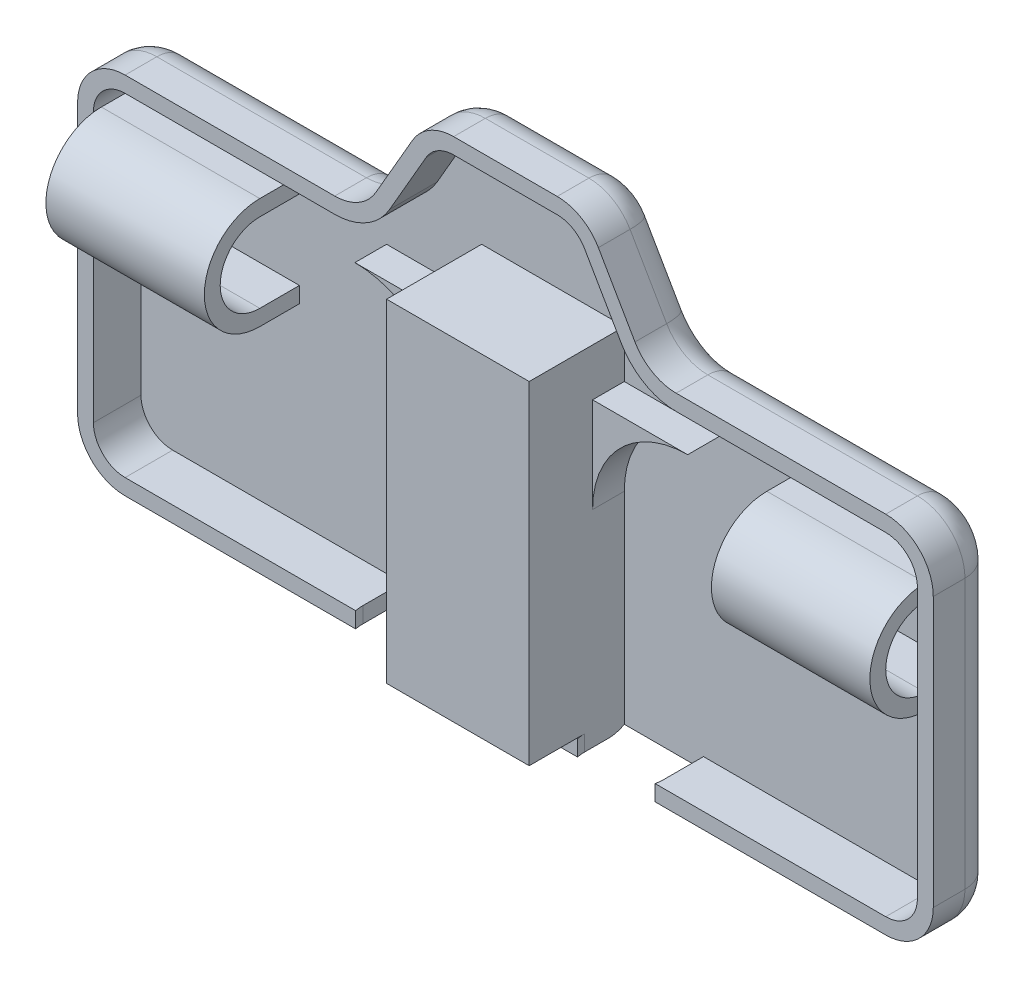
SolidWorks part; units mm, degrees
material "PA Type 6"
ref_plane "Front Plane" through (0, 0, 0) normal (0, 0, 1) x (1, 0, 0)
ref_plane "Top Plane" through (0, 0, 0) normal (0, 1, 0) x (1, 0, 0)
ref_plane "Right Plane" through (0, 0, 0) normal (1, 0, 0) x (0, 0, -1)
sketch "Sketch2" plane through (0, 0, 0) normal (0, 0, 1) x (1, 0, 0)
  line L0 (-3.2679, 18.5) -> (3.2679, 18.5)
  line L1 (-24, 11.5) -> (-10.7735, 11.5)
  line L2 (-27, 8.5) -> (-27, -8.5)
  line L3 (-24, -11.5) -> (24, -11.5)
  line L4 (27, 8.5) -> (27, -8.5)
  line L5 (-27, 11.5) -> (27, -11.5) construction
  line L6 (-27, -11.5) -> (27, 11.5) construction
  line L7 (-5.866, 17) -> (-8.1754, 13)
  line L8 (5.866, 17) -> (8.1754, 13)
  line L9 (10.7735, 11.5) -> (24, 11.5)
  arc A0 (24, -11.5) -> (27, -8.5) centre (24, -8.5) ccw
  arc A1 (-27, -8.5) -> (-24, -11.5) centre (-24, -8.5) ccw
  arc A2 (24, 11.5) -> (27, 8.5) centre (24, 8.5) cw
  arc A3 (8.1754, 13) -> (10.7735, 11.5) centre (10.7735, 14.5) ccw
  arc A4 (3.2679, 18.5) -> (5.866, 17) centre (3.2679, 15.5) cw
  arc A5 (-3.2679, 18.5) -> (-5.866, 17) centre (-3.2679, 15.5) ccw
  arc A6 (-8.1754, 13) -> (-10.7735, 11.5) centre (-10.7735, 14.5) cw
  arc A7 (-24, 11.5) -> (-27, 8.5) centre (-24, 8.5) ccw
  point P0 (0, 0)
  point P8 (0, 18.5)
  point P22 (9.0415, 11.5)
  point P25 (5, 18.5)
  point P28 (-5, 18.5)
  dimension "D6" = 3
  dimension "D1" = 54
  dimension "D2" = 23
  dimension "D3" = 10
  dimension "D4" = 7
  dimension "D5" = 60
extrude "Boss-Extrude1" add sketch "Sketch2" along normal blind 4
shell "Shell1" thickness 1 removed face at (0, 7.5, 4)
sketch "Sketch3" plane through (0, 0, 0) normal (1, 0, 0) x (0, 0, -1)
  line L0 (-1, -8.5) -> (-1, -10.5) construction
  line L2 (-3.5, 2.5) -> (-1, 2.5)
  line L3 (-3.5, 7.5) -> (-1, 7.5)
  line L4 (-1, 2.5) -> (-1, 7.5)
  line L8 (0, 1.5) -> (0, 8.5) construction
  line L9 (-3.5, 8.5) -> (0, 8.5) construction
  line L10 (-3.5, 1.5) -> (0, 1.5) construction
  line L11 (-3.5, 1.5) -> (-1, 1.5)
  line L12 (-3.5, 8.5) -> (-1, 8.5)
  line L13 (-1, 1.5) -> (-1, 2.5)
  line L14 (-1, 8.5) -> (-1, 7.5)
  line L15 (-6.6721, 6.4792) -> (-5.7658, 6.0565)
  line L16 (-4, 8.5) -> (-1, 8.5) construction
  arc A0 (-3.5, 7.5) -> (-3.5, 2.5) centre (-3.5, 5) ccw
  arc A1 (-3.5, 8.5) -> (-3.5, 1.5) centre (-3.5, 5) ccw
  arc A2 (-3.5, 7.5) -> (-3.5, 2.5) centre (-3.5, 5) ccw construction
  dimension "D1" = 5
  dimension "D2" = 3.5
  dimension "D4" = 25
  dimension "D3" = 1
extrude "Boss-Extrude2" add sketch "Sketch3" along normal blind 10 from surface contours A1 L11 L13 L2 A0 | L12 A1 A0 L3 L14 region at (0, 2.422, 2.25) region at (0, 7.665, 3.859) starting at face at (-26, 0, 2.5)
extrude "Boss-Extrude3" add sketch "Sketch3<3>" against normal blind 10 from surface contours L12 A1 A0 L3 L14 | A1 L11 L13 L2 A0 region at (0, 2.422, 2.25) region at (0, 7.665, 3.859) starting at face at (26, 0, 2.5)
sketch "Sketch3<3>" plane through (0, 0, 0) normal (1, 0, 0) x (0, 0, -1) same geometry as "Sketch3"
sketch "Sketch4" plane through (0, 0, 1) normal (0, 0, 1) x (1, 0, 0)
  line L0 (-24, -10.5) -> (24, -10.5) construction
  line L1 (-4.5, 10.5) -> (4.5, 10.5)
  line L2 (-4.5, 10.5) -> (-4.5, -10.5)
  line L3 (-4.5, -10.5) -> (4.5, -10.5)
  line L4 (4.5, 10.5) -> (4.5, -10.5)
  line L5 (-4.5, 10.5) -> (4.5, -10.5) construction
  line L6 (-4.5, -10.5) -> (4.5, 10.5) construction
  line L7 (-16, 7.5) -> (-26, 7.5) construction
  line L8 (0, -3.85) -> (0, 3.85) construction
  line L9 (-10.5, 7.5) -> (-4.5, 7.5)
  line L10 (10.5, 7.5) -> (4.5, 7.5)
  arc A0 (-10.5, 7.5) -> (-4.5, 1.5) centre (-10.5, 1.5) cw
  arc A1 (10.5, 7.5) -> (4.5, 1.5) centre (10.5, 1.5) ccw
  point P0 (0, 0)
  line M6 (-16, 7.5) -> (-26, 7.5)
  line M13 (-24, -10.5) -> (24, -10.5)
  dimension "D2" = 6
  dimension "D1" = 9
extrude "Boss-Extrude5" add sketch "Sketch4" along normal blind 2 contours L9 A0 L2 | A1 L10 L4 region at (-5.8402, 6.1598, 1) region at (5.8402, 6.1598, 1)
extrude "Boss-Extrude6" add sketch "Sketch4<3>" along normal blind 6 contours L4 L2 M6 M13 | L2 L1 L4 L3 region at (0, 0, 1)
sketch "Sketch4<3>" plane through (0, 0, 1) normal (0, 0, 1) x (1, 0, 0) same geometry as "Sketch4"
sketch "Sketch5" plane through (0, 0, 0) normal (0, 1, 0) x (1, 0, 0)
  line L0 (-24, -1) -> (-4.5, -1) construction
  line L1 (-4.5, -3) -> (-4.5, -1) construction
  line L2 (-9.5, -3.5) -> (-9.5, -1)
  line L3 (-4.5, -3.5) -> (-4.5, -1)
  line L4 (-9.5, -1) -> (-4.5, -1)
  line L5 (0, -3.85) -> (0, 3.85) construction
  line L6 (4.5, -3.5) -> (4.5, -1)
  line L7 (9.5, -1) -> (4.5, -1)
  line L8 (9.5, -3.5) -> (9.5, -1)
  arc A0 (-9.5, -3.5) -> (-4.5, -3.5) centre (-7, -3.5) ccw
  arc A1 (9.5, -3.5) -> (4.5, -3.5) centre (7, -3.5) cw
  dimension "D1" = 5
extrude "Cut-Extrude1" cut sketch "Sketch5" against normal up to next
fillet "Fillet1" radius 2 16 edges at (27, 0, 0) (26.1213, 10.6213, 0) (17.3868, 11.5, 0) (9.2735, 11.9019, 0) (7.0207, 15, 0) (4.7679, 18.0981, 0) (0, 18.5, 0) (-4.7679, 18.0981, 0) (-7.0207, 15, 0) (-9.2735, 11.9019, 0) (-17.3868, 11.5, 0) (-26.1213, 10.6213, 0) (-27, 0, 0) (-26.1213, -10.6213, 0) (0, -11.5, 0) (26.1213, -10.6213, 0)
